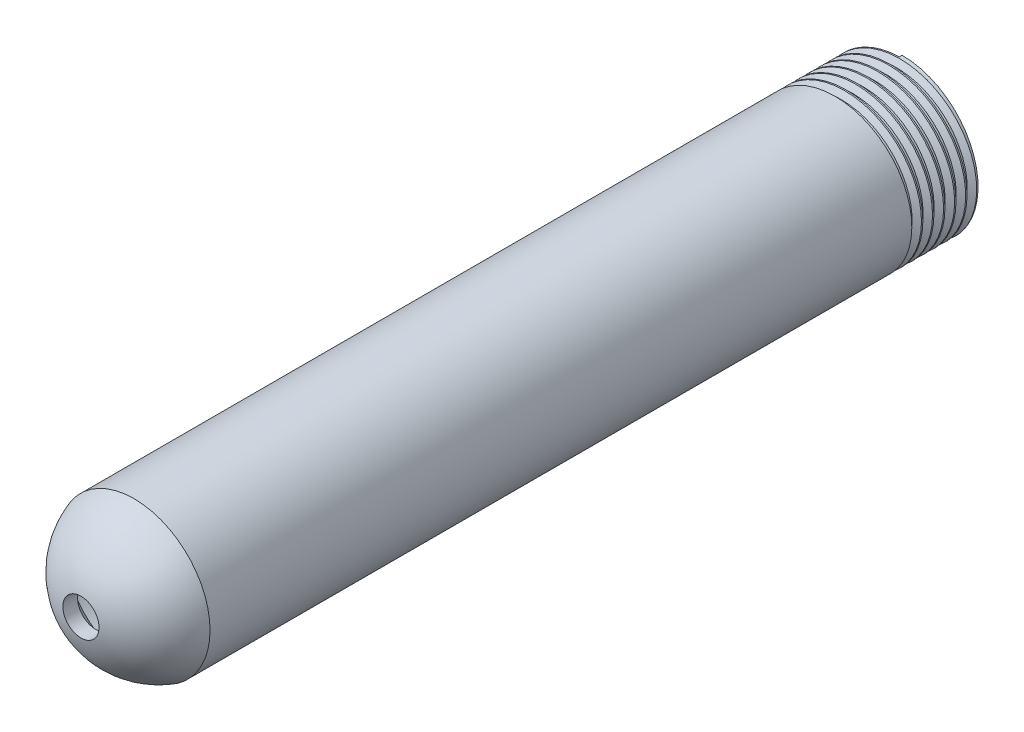
SolidWorks part; units mm, degrees
ref_plane "Alzado" through (0, 0, 0) normal (0, 0, 1) x (1, 0, 0)
ref_plane "Planta" through (0, 0, 0) normal (0, 1, 0) x (1, 0, 0)
ref_plane "Vista lateral" through (0, 0, 0) normal (1, 0, 0) x (0, 0, -1)
sketch "Croquis1" plane through (0, 0, 0) normal (0, 0, 1) x (1, 0, 0)
  circle A0 centre (0, 0) radius 27.5
  dimension "D1" = 55
extrude "Saliente-Extruir1" add sketch "Croquis1" along normal blind 26
thread "Rosca1" pitch 4 method cut profile "Perfil de rosca1" start angle 0, offset 0, length 25, pitch 4, diameter 55
ref_plane "Plano1" through (-27.5, 0, 26) normal (0, -1, 0) x (-1, 0, 0)
sketch "Perfil de rosca1" plane through (-27.5, 0, 26) normal (0, -1, 0) x (-1, 0, 0)
  line L0 (0, 0) -> (0, 4) construction
  line L11 (0, 0) -> (0, 3.5)
  line L12 (0, 3.5) -> (-2.1651, 2.25)
  line L13 (-2.1651, 2.25) -> (-2.1651, 1.25)
  line L15 (-2.1651, 1.25) -> (0, 0)
  line L17 (-2.1651, 1.75) -> (0, 1.75) construction
  point P2 (0, 0)
  dimension "Pitch" = 4
  dimension "Profile_Angle" = 60
  dimension "Profile_Land" = 1
  dimension "Profile_Height" = 2.1651
sketch "Croquis4" plane through (0, 0, 26) normal (0, 0, 1) x (1, 0, 0)
  circle A0 centre (0, 0) radius 25.25
  dimension "D1" = 50.5
extrude "Cortar-Extruir1" cut sketch "Croquis4" against normal blind 26
sketch "Croquis5" plane through (0, 0, 26) normal (0, 0, 1) x (1, 0, 0)
  circle A0 centre (0, 0) radius 27.5
  circle A1 centre (0, 0) radius 25.5
  dimension "D1" = 55
  dimension "D2" = 51
extrude "Saliente-Extruir2" add sketch "Croquis5" along normal blind 2
sketch "Croquis6" plane through (0, 0, 28) normal (0, 0, 1) x (1, 0, 0)
  circle A0 centre (0, 0) radius 27.5
  circle A1 centre (0, 0) radius 25.5
  dimension "D1" = 51
  dimension "D2" = 55
extrude "Saliente-Extruir3" add sketch "Croquis6" along normal blind 250
sketch "Croquis8" plane through (0, 0, 278) normal (0, 0, 1) x (1, 0, 0)
  circle A0 centre (0, 0) radius 27.5
  dimension "D1" = 55
extrude "Saliente-Extruir5" add sketch "Croquis8" along normal blind 0.1
ref_plane "Plano2" through (0, 0, 288.1) normal (0, 0, 1) x (1, 0, 0)
dome "Cúpula1" faces to dome 1 distance 20 reverse direction no elliptical dome no face at (27.5, 0, 278.1) parameters "D1"=20
sketch "Croquis12" plane through (0, 0, 278) normal (0, 0, -1) x (-1, 0, 0)
  circle A0 centre (0, 0) radius 6.55
  dimension "D1" = 13.1
extrude "Cortar-Extruir5" cut sketch "Croquis12" against normal blind 64
sketch "Croquis13" plane through (0, 0, 278) normal (0, 0, -1) x (-1, 0, 0)
  circle A0 centre (0, 0) radius 25.25
extrude "Cortar-Extruir6" cut sketch "Croquis13" against normal blind 14 draft 50
sketch "Croquis15" plane through (0, 0, 0) normal (0, 0, 1) x (1, 0, 0)
  circle A0 centre (0, 0) radius 25.25
